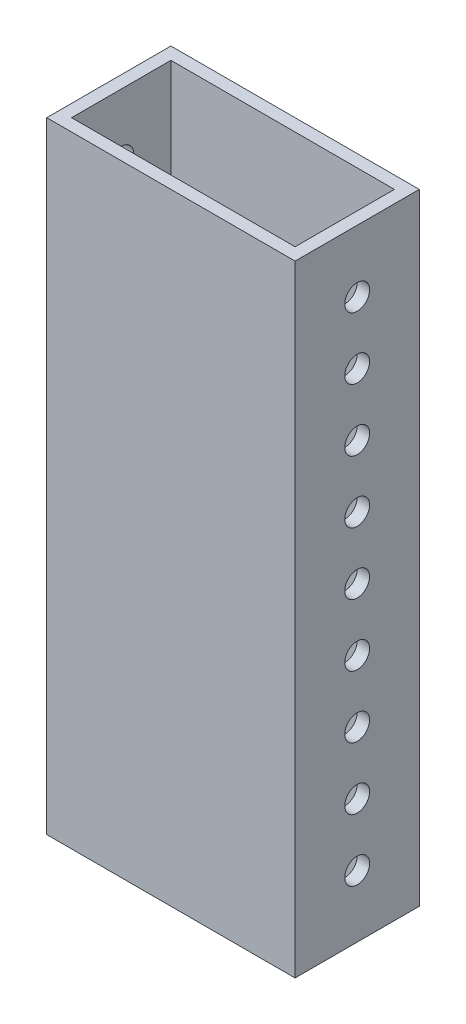
SolidWorks part; units mm, degrees
ref_plane "Front Plane" through (0, 0, 0) normal (0, 0, 1) x (1, 0, 0)
ref_plane "Top Plane" through (0, 0, 0) normal (0, 1, 0) x (1, 0, 0)
ref_plane "Right Plane" through (0, 0, 0) normal (1, 0, 0) x (0, 0, -1)
sketch "Sketch1" plane through (0, 0, 0) normal (0, 1, 0) x (1, 0, 0)
  line L1 (-59.9507, 17.7211) -> (-9.1507, 17.7211)
  line L2 (-59.9507, 17.7211) -> (-59.9507, -7.6789)
  line L3 (-59.9507, -7.6789) -> (-9.1507, -7.6789)
  line L4 (-9.1507, 17.7211) -> (-9.1507, -7.6789)
  line L5 (-59.9507, 17.7211) -> (-9.1507, -7.6789) construction
  line L6 (-59.9507, -7.6789) -> (-9.1507, 17.7211) construction
  line L7 (-57.4107, 15.1811) -> (-11.6907, 15.1811)
  line L8 (-57.4107, 15.1811) -> (-57.4107, -5.1389)
  line L9 (-57.4107, -5.1389) -> (-11.6907, -5.1389)
  line L10 (-11.6907, 15.1811) -> (-11.6907, -5.1389)
  line L11 (-57.4107, 15.1811) -> (-11.6907, -5.1389) construction
  line L12 (-57.4107, -5.1389) -> (-11.6907, 15.1811) construction
  point P0 (-34.5507, 5.0211)
  point P5 (-34.5507, 5.0211)
  dimension "D1" = 25.4
  dimension "D2" = 50.8
  dimension "D3" = 2.54
  dimension "D4" = 2.54
  dimension "D5" = 2.54
  dimension "D6" = 2.54
extrude "Boss-Extrude2" add sketch "Sketch1" along normal blind 127
sketch "Sketch2" plane through (-9.1507, 0, 0) normal (1, 0, 0) x (0, 0, -1)
  line L0 (-7.6789, 127) -> (17.7211, 127) construction
  line L1 (17.7211, 127) -> (17.7211, 0) construction
  circle A0 centre (5.0211, 114.3) radius 2.54
  circle A1 centre (5.0211, 101.6) radius 2.54
  circle A2 centre (5.0211, 88.9) radius 2.54
  circle A3 centre (5.0211, 76.2) radius 2.54
  circle A4 centre (5.0211, 63.5) radius 2.54
  circle A5 centre (5.0211, 50.8) radius 2.54
  circle A6 centre (5.0211, 38.1) radius 2.54
  circle A7 centre (5.0211, 25.4) radius 2.54
  circle A8 centre (5.0211, 12.7) radius 2.54
  dimension "D1" = 5.08
  dimension "D2" = 12.7
  dimension "D3" = 12.7
  dimension "D4" = 9
extrude "Cut-Extrude1" cut sketch "Sketch2" against normal blind 127
